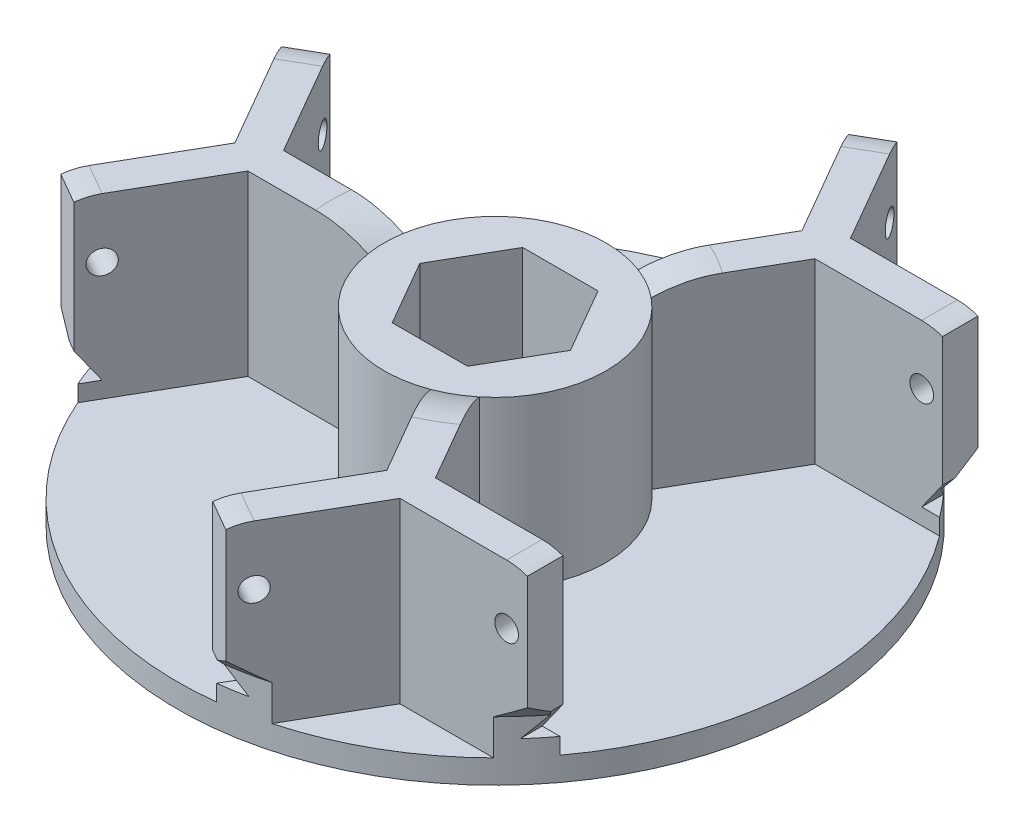
SolidWorks part; units mm, degrees
material "ABS"
ref_plane "Front Plane" through (0, 0, 0) normal (0, 0, 1) x (1, 0, 0)
ref_plane "Top Plane" through (0, 0, 0) normal (0, 1, 0) x (1, 0, 0)
ref_plane "Right Plane" through (0, 0, 0) normal (1, 0, 0) x (0, 0, -1)
sketch "Sketch2" plane through (0, 0, 0) normal (0, 1, 0) x (1, 0, 0)
  circle A0 centre (0, 0) radius 30
  dimension "D1" = 60
extrude "Boss-Extrude1" add sketch "Sketch2" along normal blind 1 and the other way blind 1
sketch "Sketch1" plane through (0, 1, 0) normal (0, 1, 0) x (1, 0, 0)
  line L0 (10.1036, 17.5) -> (0, 0) construction
  line L1 (6.3509, 0) -> (3.1754, 5.5)
  line L2 (3.1754, 5.5) -> (-3.1754, 5.5)
  line L3 (-3.1754, 5.5) -> (-6.3509, 0)
  line L4 (-6.3509, 0) -> (-3.1754, -5.5)
  line L5 (-3.1754, -5.5) -> (3.1754, -5.5)
  line L6 (3.1754, -5.5) -> (6.3509, 0)
  line L7 (10.1036, 17.5) -> (2.972, 29.8524) construction
  line L8 (10.1036, 17.5) -> (24.367, 17.5) construction
  line L9 (8.3716, 17.5) -> (1.1678, 29.9773)
  line L10 (8.3716, 17.5) -> (3.3158, 8.7432)
  line L11 (5.8437, 13.1216) -> (8.4418, 11.6216) construction
  line L12 (5.9139, 7.2432) -> (10.9697, 16)
  line L13 (10.9697, 16) -> (25.3772, 16)
  line L14 (23.2164, 19) -> (10.9697, 19)
  line L15 (10.9697, 19) -> (4.8463, 29.606)
  line L16 (3.6042, 31.7573) -> (1.0062, 30.2573) construction
  line L17 (13.9732, 19) -> (13.9732, 16) construction
  line L18 (21.7164, 19) -> (21.7164, 16)
  line L19 (2.9982, 26.8069) -> (5.5963, 28.3069)
  circle A0 centre (0, 0) radius 5.5 construction
  circle A1 centre (0, 0) radius 6.3509 construction
  circle A2 centre (0, 0) radius 9.3509
  circle A3 centre (0, 0) radius 30
  point P27 (7.1427, 12.3716)
  point P32 (2.3052, 31.0073)
  point P35 (13.9732, 17.5)
  circle M11 centre (0, 0) radius 30
  dimension "D3" = 60
  dimension "D1" = 11
  dimension "D4" = 3
  dimension "D5" = 16
  dimension "D6" = 1.5
  dimension "D7" = 1.5
  dimension "D2" = 3
extrude "Boss-Extrude2" add sketch "Sketch1" along normal blind 14 contours A2 L6 L5 L4 L3 L2 L1 region at (4.5432, 1, -7.869)
extrude "Boss-Extrude3" add sketch "Sketch1<3>" along normal blind 15 contours A2 L12 L13 L14 L10 M11 region at (10.2264, 1, -17.7126)
sketch "Sketch1<3>" plane through (0, 1, 0) normal (0, 1, 0) x (1, 0, 0) same geometry as "Sketch1"
pattern_circular "CirPattern1" count 3 over 360 about axis through (0, 1, 0) along (0, 1, 0) of "Boss-Extrude3"
sketch "Sketch3" plane through (-16.4545, 0, 9.5) normal (-0.866, 0, 0.5) x (0.5, 0, 0.866)
  line L0 (-24.0444, 8.1023) -> (-19.9697, 2.3724)
  line L4 (-19.9697, 2.3724) -> (-27.16, 2.3724)
  line L6 (-19.9697, 16) -> (-17.4531, 19.1644)
  arc A0 (-19.9697, 16) -> (-24.0444, 8.1023) centre (-19.9697, 11) ccw
  circle A3 centre (-19.9697, 11) radius 5 construction
  point P13 (46.2722, -7.9262)
extrude "Cut-Extrude2" cut sketch "Sketch3" against normal through all and the other way through all
sketch "Sketch4" plane through (-16.4545, 0, 9.5) normal (-0.866, 0, 0.5) x (0.5, 0, 0.866)
  line L0 (-21.7164, 1) -> (-10.9697, 1) construction
  line L1 (-10.9697, 16) -> (-10.9697, 1) construction
  circle A0 centre (-19.9697, 11) radius 1
  dimension "D1" = 2
  dimension "D2" = 10
  dimension "D3" = 9
extrude "Cut-Extrude3" cut sketch "Sketch4" against normal blind 43
pattern_circular "CirPattern2" count 3 over 360 about axis through (0, 1, 0) along (0, 1, 0) of "Cut-Extrude2", "Cut-Extrude3"
sketch "Sketch5" plane through (0, 0, 0) normal (1, 0, 0) x (0, 0, -1)
  line L0 (-30, -1) -> (30, -1) construction
  line L1 (0, -1000) -> (0, 49000) construction
  line L3 (-31.7779, -1) -> (-26.7779, -1)
  line L4 (-26.7779, 4) -> (-26.7779, -1)
  line L5 (-26.7779, 4) -> (-31.7779, 9)
  line L7 (-31.7779, 9) -> (-31.7779, -1)
  line L8 (-31.7779, 9) -> (-31.7779, -1)
  dimension "D1" = 45
  dimension "D2" = 5
  dimension "D3" = 10
ref_axis "Axis1" through (0, 0, 0) along (0, 1, 0)
revolve "Cut-Revolve2" cut sketch "Sketch5" angle 360 about L1 region at (0, 2.8889, 29.5556)
extrude "Cut-Extrude4" cut sketch "Sketch1<4>" against normal blind 43 contours L5 L6 L1 L2 L3 L4 region at (0, 1, 0)
sketch "Sketch1<4>" plane through (0, 1, 0) normal (0, 1, 0) x (1, 0, 0) same geometry as "Sketch1"
fillet "Fillet1" radius 10 3 edges at (4.6754, 16, 8.0981) (-9.3509, 16, 0) (4.6754, 16, -8.0981)
